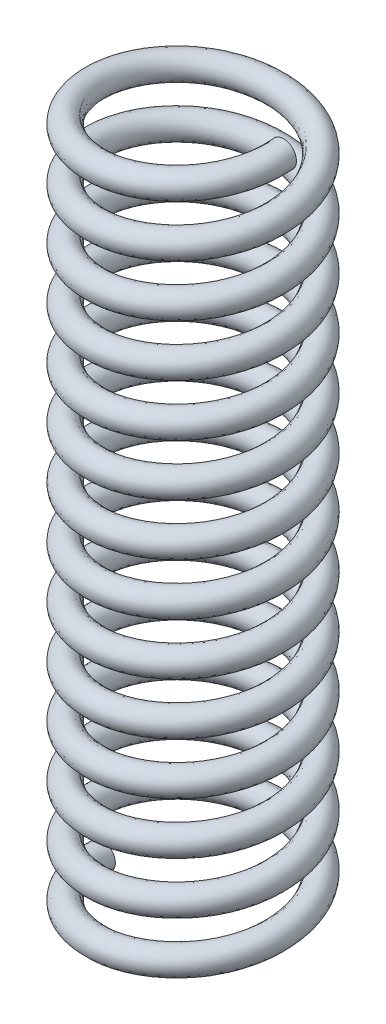
SolidWorks part; units mm, degrees
note: '?' marks a value the reader was unsure of.
material "AISI 304"
ref_plane "Front Plane" through (0, 0, 0) normal (0, 0, 1) x (1, 0, 0)
ref_plane "Top Plane" through (0, 0, 0) normal (0, 1, 0) x (1, 0, 0)
ref_plane "Right Plane" through (0, 0, 0) normal (1, 0, 0) x (0, 0, -1)
ref_axis "SpringAxis" through (0, 1.15, 0) along (0, -1, 0)?
sketch "SpringBodyDiameterS" plane through (0, 0, 0) normal (0, 0, 1) x (1, 0, 0)
  line L0 (0, 0) -> (1.5, 0) construction
  line L1 (0, 0) -> (0, 1) construction
  line L2 (1.75, 0) -> (2, 0) construction
  circle A0 centre (1.75, 0) radius 0.25
  dimension "WireDia" = 0.5
  dimension "RefRevolve" = 1
  dimension "RevolveDia" = 3.5
  dimension "RefID" = 1.5
  dimension "RefOD" = 2
sketch "SpringHelixS" plane through (0, 0, 0) normal (0, 1, 0) x (1, 0, 0)
  circle A0 centre (0, 0) radius 1.75
  dimension "RefDia" = 3.5
curve "SPRING HELIX" pitch 1 height 13.5 turns 13.5 parameters "Height"=13.5, "Pitch"=1
sweep "SPRING" add profiles "SpringBodyDiameterS" path "SPRING HELIX"
